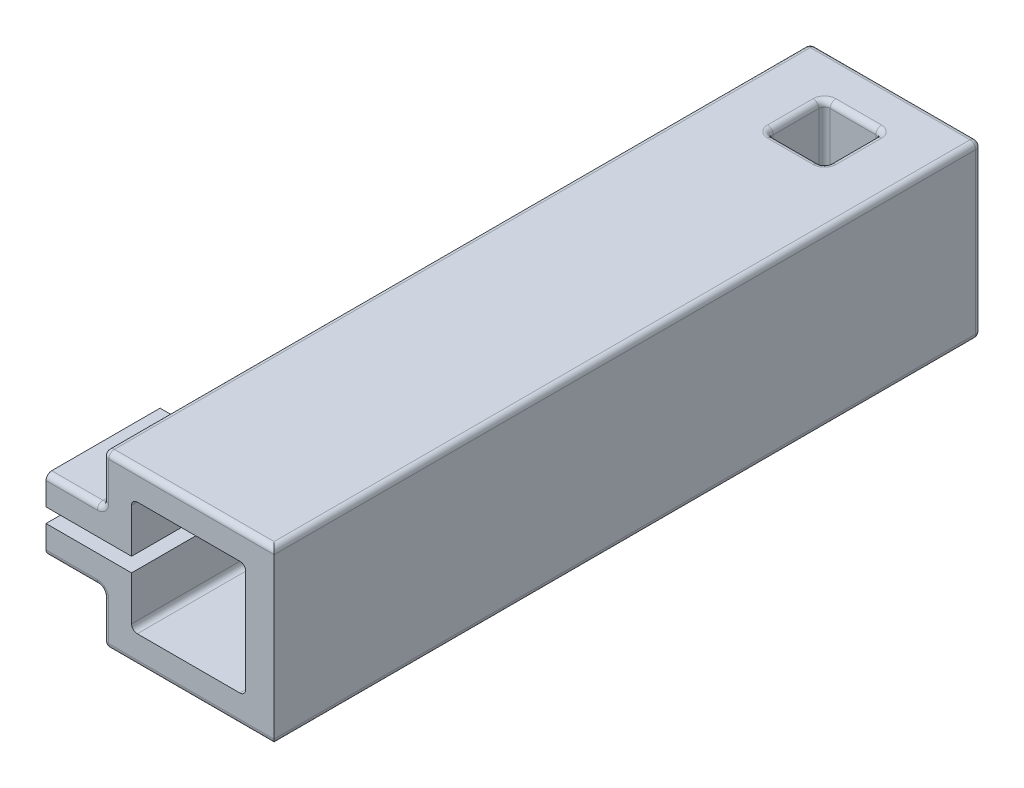
SolidWorks part; units mm, degrees
material "20% infill ABS"
ref_plane "Front Plane" through (0, 0, 0) normal (0, 0, 1) x (1, 0, 0)
ref_plane "Top Plane" through (0, 0, 0) normal (0, 1, 0) x (1, 0, 0)
ref_plane "Right Plane" through (0, 0, 0) normal (1, 0, 0) x (0, 0, -1)
sketch "Sketch1" plane through (0, 0, 0) normal (0, 0, 1) x (1, 0, 0)
  line L0 (-21.017, 13.2451) -> (-1.017, -6.7549)
  line L1 (-21.017, 13.2451) -> (-1.017, 13.2451)
  line L2 (-21.017, 13.2451) -> (-21.017, -6.7549)
  line L3 (-21.017, -6.7549) -> (-1.017, -6.7549)
  line L4 (-1.017, 13.2451) -> (-1.017, -6.7549)
  line L5 (-11.017, 3.2451) -> (-23.017, 3.2451)
  line L6 (-23.017, 15.2451) -> (0.983, 15.2451)
  line L7 (-23.017, 15.2451) -> (-23.017, -8.7549)
  line L8 (-23.017, -8.7549) -> (0.983, -8.7549)
  line L9 (0.983, 15.2451) -> (0.983, -8.7549)
  line L10 (-23.017, 15.2451) -> (0.983, -8.7549) construction
  line L11 (-23.017, -8.7549) -> (0.983, 15.2451) construction
  line L12 (-23.017, 3.2451) -> (-21.017, 3.2451)
  line L13 (-21.017, 4.5033) -> (-33.017, 4.5033)
  line L14 (-23.017, 4.5033) -> (-21.017, 4.5033)
  line L15 (-23.017, 4.5033) -> (-23.017, 1.9869)
  line L16 (-23.017, 1.9869) -> (-21.017, 1.9869)
  line L17 (-21.017, 4.5033) -> (-21.017, 1.9869)
  line L18 (-23.017, 4.5033) -> (-21.017, 1.9869) construction
  line L19 (-23.017, 1.9869) -> (-21.017, 4.5033) construction
  line L20 (-21.017, 1.9869) -> (-33.017, 1.9869)
  line L21 (-33.017, 4.5033) -> (-33.017, 6.5033)
  line L22 (-33.017, 1.9869) -> (-33.017, -0.0131)
  line L23 (-33.017, -0.0131) -> (-23.017, -0.0131)
  line L24 (-33.017, 6.5033) -> (-23.017, 6.5033)
  line L25 (-33.017, 1.9869) -> (-23.017, 1.9869)
  line L26 (-23.017, 1.9869) -> (-33.017, 1.9869)
  point P4 (-11.017, 3.2451)
  point P11 (-22.017, 3.2451)
  dimension "D1" = 20
  dimension "D2" = 20
  dimension "D3" = 24
  dimension "D4" = 24
extrude "Boss-Extrude1" add sketch "Sketch1" along normal blind 25 contours L16 L7 L8 L9 L6 L13 L2 L1 L4 L3 region at (-21.3564, 8.8742, 0)
sketch "Sketch2" plane through (-23.017, 0, 0) normal (-1, 0, 0) x (0, 0, 1)
  line L0 (25, 15.2451) -> (25, 4.5033) construction
  line L1 (0, 4.5033) -> (25, 4.5033)
  line L2 (0, 4.5033) -> (0, 6.5033)
  line L3 (0, 6.5033) -> (25, 6.5033)
  line L4 (25, 4.5033) -> (25, 6.5033)
  line L5 (25, 1.9869) -> (25, -8.7549) construction
  line L6 (0, 1.9869) -> (25, 1.9869)
  line L7 (0, 1.9869) -> (0, -0.0131)
  line L8 (0, -0.0131) -> (25, -0.0131)
  line L9 (25, 1.9869) -> (25, -0.0131)
  dimension "D1" = 2
  dimension "D2" = 2
extrude "Boss-Extrude2" add sketch "Sketch2" along normal blind 10 contours L2 L1 L4 L3 | L7 L6 L9 L8
sketch "Sketch3" plane through (0, 6.5033, 0) normal (0, 1, 0) x (1, 0, 0)
  line L0 (-23.017, 0) -> (-33.017, -25)
  circle A0 centre (-28.017, -12.5) radius 2.5
extrude "Cut-Extrude1" cut sketch "Sketch3" against normal blind 20 contours L0 A0 | L0 A0 region at (-27.0319, 6.5033, 12.8941) region at (-29.0022, 6.5033, 12.1059)
sketch "Sketch4" plane through (0, 6.5033, 0) normal (0, 1, 0) x (1, 0, 0)
  line L0 (-33.017, -25) -> (-32.017, -25)
  line L1 (-33.017, -25) -> (-23.017, -25) construction
  line L2 (-32.017, -25) -> (-32.017, -24)
  line L3 (-32.017, -24) -> (-33.017, -24)
  line L4 (-33.017, -24) -> (-33.017, -25)
  circle A0 centre (-32.017, -24) radius 1
  line M4 (-33.017, 0) -> (-33.017, -25)
  line M5 (-33.017, -25) -> (-23.017, -25)
extrude "Cut-Extrude2" cut sketch "Sketch4" against normal blind 20 contours A0 M4 M5 region at (-32.7937, 6.5033, 24.7766)
sketch "Sketch5" plane through (0, 6.5033, 0) normal (0, 1, 0) x (1, 0, 0)
  line L0 (-33.017, 0) -> (-32.017, 0)
  line L1 (-33.017, 0) -> (-23.017, 0) construction
  line L2 (-32.017, 0) -> (-32.017, -1)
  line L3 (-32.017, -1) -> (-33.017, -1)
  line L4 (-33.017, 0) -> (-33.017, -24) construction
  line L5 (-33.017, -1) -> (-33.017, 0)
  circle A0 centre (-32.017, -1) radius 1
  line M2 (-33.017, 0) -> (-33.017, -24)
  line M6 (-23.017, 0) -> (-33.017, 0)
extrude "Cut-Extrude3" cut sketch "Sketch5" against normal blind 20 contours A0 M6 M2 region at (-32.7937, 6.5033, 0.2234)
sketch "Sketch6" plane through (0, 0, 25) normal (0, 0, 1) x (1, 0, 0)
  line L0 (-21.017, 13.2451) -> (-21.017, 12.2451)
  line L1 (-21.017, 13.2451) -> (-21.017, 4.5033) construction
  line L2 (-21.017, 13.2451) -> (-20.017, 13.2451)
  line L3 (-21.017, 13.2451) -> (-1.017, 13.2451) construction
  line L4 (-21.017, 12.2451) -> (-20.017, 12.2451)
  line L5 (-20.017, 12.2451) -> (-20.017, 13.2451)
  circle A0 centre (-20.017, 12.2451) radius 1
  line M11 (-21.017, 4.5033) -> (-21.017, 13.2451)
  line M12 (-21.017, 13.2451) -> (-1.017, 13.2451)
extrude "Boss-Extrude4" add sketch "Sketch6" against normal blind 25 contours A0 M12 M11 region at (-20.7937, 13.0217, 25)
sketch "Sketch7" plane through (0, 0, 25) normal (0, 0, 1) x (1, 0, 0)
  line L0 (-1.017, 13.2451) -> (-1.017, 12.2451)
  line L1 (-1.017, 13.2451) -> (-1.017, -6.7549) construction
  line L2 (-1.017, 12.2451) -> (-2.017, 12.2451)
  line L3 (-2.017, 12.2451) -> (-2.017, 13.2451)
  line L4 (-20.017, 13.2451) -> (-1.017, 13.2451) construction
  line L5 (-1.017, 13.2451) -> (-2.017, 13.2451)
  circle A0 centre (-2.017, 12.2451) radius 1
  line M3 (-20.017, 13.2451) -> (-1.017, 13.2451)
  line M4 (-1.017, 13.2451) -> (-1.017, -6.7549)
extrude "Boss-Extrude5" add sketch "Sketch7" against normal blind 25 contours A0 M4 M3 region at (-1.2404, 13.0217, 25)
sketch "Sketch9" plane through (0, 0, 25) normal (0, 0, 1) x (1, 0, 0)
  line L0 (-1.017, -6.7549) -> (-2.017, -6.7549)
  line L1 (-21.017, -6.7549) -> (-1.017, -6.7549) construction
  line L2 (-1.017, -6.7549) -> (-1.017, -5.7549)
  line L3 (-1.017, 12.2451) -> (-1.017, -6.7549) construction
  line L4 (-1.017, -5.7549) -> (-2.017, -5.7549)
  line L5 (-2.017, -6.7549) -> (-2.017, -5.7549)
  circle A0 centre (-2.017, -5.7549) radius 1
  line M5 (-1.017, 12.2451) -> (-1.017, -6.7549)
  line M6 (-1.017, -6.7549) -> (-21.017, -6.7549)
extrude "Boss-Extrude6" add sketch "Sketch9" against normal blind 25 contours A0 M6 M5 region at (-1.2404, -6.5315, 25)
sketch "Sketch10" plane through (0, 0, 25) normal (0, 0, 1) x (1, 0, 0)
  line L0 (-21.017, -6.7549) -> (-20.017, -6.7549)
  line L1 (-21.017, -6.7549) -> (-2.017, -6.7549) construction
  line L2 (-21.017, -6.7549) -> (-21.017, -5.7549)
  line L3 (-21.017, 1.9869) -> (-21.017, -6.7549) construction
  line L4 (-20.017, -6.7549) -> (-20.017, -5.7549)
  line L5 (-20.017, -5.7549) -> (-21.017, -5.7549)
  circle A0 centre (-20.017, -5.7549) radius 1
  line M11 (-2.017, -6.7549) -> (-21.017, -6.7549)
  line M12 (-21.017, -6.7549) -> (-21.017, 1.9869)
extrude "Boss-Extrude7" add sketch "Sketch10" against normal blind 25 contours A0 M12 M11 region at (-20.7937, -6.5315, 25)
fillet "Fillet1" radius 1 4 edges at (-23.017, 15.2451, 12.5) (-23.017, -8.7549, 12.5) (0.983, -8.7549, 12.5) (0.983, 15.2451, 12.5)
fillet "Fillet2" radius 1 28 edges at (-23.017, 10.3742, 0) (-22.7241, 14.9522, 0) (-23.017, -3.884, 0) (-22.7241, -8.462, 0) (-11.017, -8.7549, 0) (0.6901, -8.462, 0) (0.983, 3.2451, 0) (0.6901, 14.9522, 0) (-27.517, 6.5033, 0) (-32.7241, 6.5033, 0.2929) (-32.7241, 6.5033, 24.7071) (-27.517, -0.0131, 0) (-32.7241, -0.0131, 0.2929) (-32.7241, -0.0131, 24.7071) (-11.017, 15.2451, 0) (-33.017, 6.5033, 12.5) (-33.017, -0.0131, 12.5) (-27.517, 6.5033, 25) (-27.517, -0.0131, 25) (-23.017, -3.884, 25) (-22.7241, -8.462, 25) (-11.017, -8.7549, 25) (0.6901, -8.462, 25) (0.983, 3.2451, 25) (0.6901, 14.9522, 25) (-11.017, 15.2451, 25) (-22.7241, 14.9522, 25) (-23.017, 10.3742, 25)
sketch "Sketch11" plane through (0, 15.2451, 0) normal (0, 1, 0) x (1, 0, 0)
  line L0 (-22.017, -1) -> (-0.017, -24)
  line L2 (-16.017, -17.5) -> (-6.017, -17.5)
  line L3 (-16.017, -17.5) -> (-16.017, -7.5)
  line L4 (-16.017, -7.5) -> (-6.017, -7.5)
  line L5 (-6.017, -17.5) -> (-6.017, -7.5)
  line L6 (-16.017, -17.5) -> (-6.017, -7.5) construction
  line L7 (-16.017, -7.5) -> (-6.017, -17.5) construction
  line L8 (-17.517, -6) -> (-4.517, -6)
  line L9 (-17.517, -6) -> (-17.517, -19)
  line L10 (-17.517, -19) -> (-4.517, -19)
  line L11 (-4.517, -6) -> (-4.517, -19)
  line L12 (-17.517, -6) -> (-4.517, -19) construction
  line L13 (-17.517, -19) -> (-4.517, -6) construction
  point P4 (-11.017, -12.5)
  point P9 (-11.017, -12.5)
  dimension "D1" = 10
  dimension "D2" = 10
  dimension "D3" = 13
  dimension "D4" = 13
extrude "Boss-Extrude8" add sketch "Sketch11" along normal blind 25 contours L11 L8 L0 L4 L5 L2 L10 | L9 L10 L0 L2 L3 L4 L8 region at (-10.8757, 15.2451, 6.1819) region at (-16.6484, 15.2451, 6.8757)
fillet "Fillet3" radius 1 4 edges at (-17.517, 27.7451, 6) (-4.517, 27.7451, 6) (-17.517, 27.7451, 19) (-4.517, 27.7451, 19)
ref_plane "Plane1" through (0, 0, 1) normal (0, 0, -1) x (-1, 0, 0)
sketch "Sketch12" plane through (0, 0, 1) normal (0, 0, -1) x (-1, 0, 0)
  line L0 (0.017, 15.2451) -> (22.017, 15.2451)
  line L1 (23.017, 14.2451) -> (23.017, 6.5033)
  line L2 (23.017, 6.5033) -> (32.017, 6.5033)
  line L3 (33.017, 5.5033) -> (33.017, 4.5033)
  line L4 (33.017, 4.5033) -> (21.017, 4.5033)
  line L5 (21.017, 4.5033) -> (21.017, 12.2451)
  line L6 (20.017, 13.2451) -> (2.017, 13.2451)
  line L7 (1.017, 12.2451) -> (1.017, -5.7549)
  line L8 (2.017, -6.7549) -> (20.017, -6.7549)
  line L9 (21.017, -5.7549) -> (21.017, 1.9869)
  line L10 (21.017, 1.9869) -> (32.017, 1.9869)
  line L11 (32.017, 1.9869) -> (33.017, 1.9869)
  line L12 (33.017, 1.9869) -> (33.017, 0.9869)
  line L13 (32.017, -0.0131) -> (23.017, -0.0131)
  line L14 (23.017, -0.0131) -> (23.017, -7.7549) construction
  line L15 (23.017, -0.0131) -> (23.017, -7.7549)
  line L16 (22.017, -8.7549) -> (0.017, -8.7549)
  line L17 (-0.983, -7.7549) -> (-0.983, 14.2451)
  line L18 (-0.983, -7.7549) -> (-0.983, 14.2451) construction
  arc A0 (0.017, 15.2451) -> (-0.983, 14.2451) centre (0.017, 14.2451) ccw construction
  arc A1 (-0.983, 14.2451) -> (0.017, 15.2451) centre (0.017, 14.2451) cw
  arc A2 (1.017, 12.2451) -> (2.017, 13.2451) centre (2.017, 12.2451) cw
  arc A3 (20.017, 13.2451) -> (21.017, 12.2451) centre (20.017, 12.2451) cw
  arc A4 (23.017, 14.2451) -> (22.017, 15.2451) centre (22.017, 14.2451) ccw
  arc A5 (32.017, 6.5033) -> (33.017, 5.5033) centre (32.017, 5.5033) cw
  arc A6 (32.017, -0.0131) -> (33.017, 0.9869) centre (32.017, 0.9869) ccw
  arc A7 (20.017, -6.7549) -> (21.017, -5.7549) centre (20.017, -5.7549) ccw
  arc A8 (22.017, -8.7549) -> (23.017, -7.7549) centre (22.017, -7.7549) ccw
  arc A9 (1.017, -5.7549) -> (2.017, -6.7549) centre (2.017, -5.7549) ccw
  arc A10 (-0.983, -7.7549) -> (0.017, -8.7549) centre (0.017, -7.7549) ccw
extrude "Boss-Extrude9" add sketch "Sketch12" along normal blind 100
sketch "Sketch14" plane through (0, 6.5033, 0) normal (0, 1, 0) x (1, 0, 0)
  line L0 (-23.017, 99) -> (-23.017, -1)
  line L1 (-23.017, 99) -> (-23.017, -24) construction
  line L2 (-23.017, -1) -> (-23.017, 29)
  line L3 (-23.017, 29) -> (-32.017, 29)
  line L4 (-32.017, 99) -> (-32.017, -24) construction
  line L5 (-23.017, 99) -> (-23.017, 68.8479)
  line L6 (-23.017, 68.8479) -> (-32.017, 68.8479)
  circle A0 centre (-27.517, 29) radius 2.5
  circle A1 centre (-27.517, 68.8479) radius 2.5
extrude "Cut-Extrude4" cut sketch "Sketch14" against normal blind 20 contours L6 A1 | L6 A1 | L3 A0 | L3 A0 region at (-27.517, 6.5033, -27.939) region at (-27.517, 6.5033, -30.061) region at (-27.517, 6.5033, -67.7869) region at (-27.517, 6.5033, -69.9089)
sketch "Sketch15" plane through (0, 15.2451, 0) normal (0, 1, 0) x (1, 0, 0)
  line L0 (-16.017, -7.5) -> (-6.017, -17.5)
  line L1 (-16.017, -17.5) -> (-6.017, -17.5) construction
  line L2 (-6.017, -7.5) -> (-16.017, -7.5)
  line L3 (-6.017, -7.5) -> (-6.017, -17.5)
  line L4 (-6.017, -17.5) -> (-16.017, -17.5)
  line L5 (-16.017, -7.5) -> (-16.017, -17.5)
  line L6 (-6.017, -7.5) -> (-16.017, -17.5) construction
  line L7 (-6.017, -17.5) -> (-16.017, -7.5) construction
  line L8 (-16.017, -17.5) -> (-6.017, -17.5) construction
  point P4 (-11.017, -12.5)
  line M1 (-6.017, -7.5) -> (-16.017, -7.5)
  line M2 (-16.017, -7.5) -> (-16.017, -17.5)
  line M3 (-16.017, -17.5) -> (-6.017, -17.5)
  line M4 (-6.017, -17.5) -> (-6.017, -7.5)
extrude "Cut-Extrude5" cut sketch "Sketch15" against normal blind 23 contours L0 M1 M4 | L0 M2 M3 region at (-9.3504, 15.2451, 10.8333) region at (-12.6837, 15.2451, 14.1667)
sketch "Sketch16" plane through (-4.517, 0, 0) normal (1, 0, 0) x (0, 0, -1)
  line L0 (-18, 15.2451) -> (-7, 40.2451)
  line L1 (-24, 15.2451) -> (99, 15.2451) construction
  line L2 (-21.678, 40.2451) -> (-3.322, 40.2451)
  line L3 (-21.678, 40.2451) -> (-21.678, 15.2451)
  line L4 (-21.678, 15.2451) -> (-3.322, 15.2451)
  line L5 (-3.322, 40.2451) -> (-3.322, 15.2451)
  line L6 (-21.678, 40.2451) -> (-3.322, 15.2451) construction
  line L7 (-21.678, 15.2451) -> (-3.322, 40.2451) construction
  point P4 (-12.5, 27.7451)
  line M1 (-18, 15.2451) -> (-7, 15.2451)
  line M2 (-7, 15.2451) -> (-7, 40.2451)
  line M3 (-7, 40.2451) -> (-18, 40.2451)
  line M4 (-18, 40.2451) -> (-18, 15.2451)
extrude "Cut-Extrude6" cut sketch "Sketch16" against normal blind 43 contours L0 M4 M3 | L0 M1 M2 | L5 L2 L4 M2 | L3 L4 L2 M4 region at (-4.517, 31.9118, 14.3333) region at (-4.517, 23.5784, 10.6667) region at (-4.517, 27.7451, 19.839) region at (-4.517, 27.7451, 5.161)
fillet "Fillet4" radius 1 24 edges at (-33.017, 1.4869, -99) (-32.7241, 0.2798, -99) (-33.017, 5.0033, -99) (-32.7241, 6.2104, -99) (-21.017, -1.884, -99) (-20.7241, -6.462, -99) (-11.017, -6.7549, -99) (-1.3099, -6.462, -99) (-1.017, 3.2451, -99) (-1.3099, 12.9522, -99) (-21.017, 8.3742, -99) (-20.7241, 12.9522, -99) (-23.017, 10.3742, -99) (-22.7241, 14.9522, -99) (-23.017, -3.884, -99) (-22.7241, -8.462, -99) (-11.017, -8.7549, -99) (0.6901, -8.462, -99) (0.983, 3.2451, -99) (0.6901, 14.9522, -99) (-27.517, -0.0131, -99) (-27.517, 6.5033, -99) (-11.017, 13.2451, -99) (-11.017, 15.2451, -99)
sketch "Sketch17" plane through (0, -7.7549, 0) normal (0, 1, 0) x (1, 0, 0)
  line L0 (-16.017, -7.5) -> (-6.017, -7.5)
  line L1 (-6.017, -7.5) -> (-6.017, -17.5)
  line L2 (-6.017, -17.5) -> (-16.017, -17.5)
  line L3 (-16.017, -17.5) -> (-16.017, -7.5)
extrude "Cut-Extrude7" cut sketch "Sketch17" against normal blind 43
ref_plane "Plane2" through (0, 0, 25) normal (0, 0, 1) x (1, 0, 0)
sketch "Sketch18" plane through (0, 0, 25) normal (0, 0, 1) x (1, 0, 0)
  line L0 (-32.017, 4.5033) -> (-23.017, 4.5033)
  line L1 (-21.017, 4.5033) -> (-32.017, 4.5033) construction
  line L2 (-23.017, 4.5033) -> (-23.017, 6.5033)
  line L3 (-23.017, 6.5033) -> (-33.017, 6.5033)
  line L4 (-23.017, -0.0131) -> (-33.017, -0.0131)
  line L5 (-33.017, -0.0131) -> (-33.017, 6.5033)
  line L6 (-23.017, 6.5033) -> (-23.017, -0.0131)
extrude "Cut-Extrude8" cut sketch "Sketch18" against normal blind 104 contours L6 L2 L3 L5 L4 region at (-28.017, 3.2451, 25)
fillet "Fillet5" radius 1 2 edges at (-23.017, 1.4869, 25) (-23.017, 5.0033, 25)
fillet "Fillet6" radius 1 6 edges at (-33.017, 1.4869, -79) (-32.7241, 0.2798, -79) (-33.017, 5.0033, -79) (-32.7241, 6.2104, -79) (-27.517, -0.0131, -79) (-27.517, 6.5033, -79)
sketch "Sketch19" plane through (0, 6.5033, 0) normal (0, 1, 0) x (1, 0, 0)
  line L0 (-32.017, 98) -> (-23.017, 80)
  line L1 (-32.017, 80) -> (-23.017, 80) construction
  line L2 (-23.017, 80) -> (-23.017, 79) construction
  line L3 (-32.017, 80) -> (-23.017, 98)
  circle A0 centre (-27.517, 89) radius 2.5
extrude "Cut-Extrude9" cut sketch "Sketch19" against normal blind 14 contours L0 A0 L3 | L3 A0 L0 | L0 A0 L3 | L3 A0 L0 region at (-27.517, 6.5033, -90.6076) region at (-28.8635, 6.5033, -89) region at (-26.1706, 6.5033, -89) region at (-27.517, 6.5033, -87.3924)
sketch "Sketch20" plane through (0, 0, -99) normal (0, 0, -1) x (-1, 0, 0)
  line L0 (0.017, -7.7549) -> (22.017, 14.2451)
  line L1 (22.017, -7.7549) -> (0.017, 14.2451)
  line L2 (22.017, 4.5033) -> (32.017, 4.5033) construction
  line L3 (0.9804, -6.7915) -> (21.0537, -6.7915)
  line L4 (0.9804, -6.7915) -> (0.9804, 13.2818)
  line L5 (0.9804, 13.2818) -> (21.0537, 13.2818)
  line L6 (21.0537, -6.7915) -> (21.0537, 13.2818)
  line L7 (0.9804, -6.7915) -> (21.0537, 13.2818) construction
  line L8 (0.9804, 13.2818) -> (21.0537, -6.7915) construction
  line L9 (-3.983, -11.7549) -> (26.017, -11.7549)
  line L10 (-3.983, -11.7549) -> (-3.983, 18.2451)
  line L11 (-3.983, 18.2451) -> (26.017, 18.2451)
  line L12 (26.017, -11.7549) -> (26.017, 18.2451)
  line L13 (-3.983, -11.7549) -> (26.017, 18.2451) construction
  line L14 (-3.983, 18.2451) -> (26.017, -11.7549) construction
  line L15 (21.017, 1.9869) -> (26.017, 1.9869)
  line L16 (21.017, 1.9869) -> (21.017, 4.5033)
  line L17 (21.017, 4.5033) -> (26.017, 4.5033)
  line L18 (26.017, 1.9869) -> (26.017, 4.5033)
  point P8 (11.017, 3.2451)
  point P13 (11.017, 3.2451)
  line M2 (0.017, -7.7549) -> (2.017, -7.7549)
  arc M3 (2.017, -7.7549) -> (0.017, -5.7549) centre (2.017, -5.7549) cw
  line M4 (0.017, -5.7549) -> (0.017, -7.7549)
  dimension "D1" = 30
extrude "Boss-Extrude10" add sketch "Sketch20" against normal blind 124 contours L6 L17 L12 L11 L10 L9 L15 L3 L4 L5 M3 M2 M4 region at (-11.017, -7.2158, -99)
sketch "Sketch21" plane through (0, -11.7549, 0) normal (0, -1, 0) x (-1, 0, 0)
  line L0 (-3.983, 99) -> (11.017, 99)
  line L1 (-3.983, 99) -> (26.017, 99) construction
  line L2 (11.017, 99) -> (11.017, 91.5)
  line L3 (11.017, 91.5) -> (16.017, 91.5)
  line L4 (16.017, 91.5) -> (16.017, 81.5)
  line L5 (16.017, 81.5) -> (6.017, 81.5)
  line L6 (6.017, 81.5) -> (6.017, 91.5)
  line L7 (6.017, 91.5) -> (11.017, 91.5)
extrude "Cut-Extrude10" cut sketch "Sketch21" against normal blind 124 contours L7 L6 L5 L4 L3 region at (-11.017, -11.7549, -86.5)
sketch "Sketch22" plane through (0, 0, -99) normal (0, 0, -1) x (-1, 0, 0)
  line L0 (26.017, 1.9869) -> (26.017, 4.5033)
  line L2 (26.017, 1.9869) -> (36.017, 1.9869)
  line L3 (26.017, 1.9869) -> (26.017, -3.0131)
  line L4 (26.017, -3.0131) -> (36.017, -3.0131)
  line L5 (36.017, 1.9869) -> (36.017, -3.0131)
  line L6 (26.017, 4.5033) -> (36.017, 4.5033)
  line L7 (26.017, 4.5033) -> (26.017, 9.5033)
  line L8 (26.017, 9.5033) -> (36.017, 9.5033)
  line L9 (36.017, 4.5033) -> (36.017, 9.5033)
  line M6 (21.0537, 4.5033) -> (32.017, 4.5033)
  line M7 (32.017, 4.5033) -> (32.017, 5.5033)
  line M8 (32.017, 5.5033) -> (26.017, 5.5033)
  line M9 (26.017, 5.5033) -> (26.017, 18.2451)
  line M13 (26.017, -11.7549) -> (26.017, 0.9869)
  line M14 (26.017, 0.9869) -> (32.017, 0.9869)
  line M15 (32.017, 0.9869) -> (32.017, 1.9869)
  line M16 (32.017, 1.9869) -> (21.0537, 1.9869)
  dimension "D1" = 5
  dimension "D2" = 5
  dimension "D3" = 10
  dimension "D4" = 10
extrude "Boss-Extrude11" add sketch "Sketch22" against normal blind 20 contours L3 M16 M14 M15 | L5 L2 L4 M15 M14 M13 | L7 M6 M7 M8 | L6 L9 L8 M9 M8 M7 region at (-29.017, 5.0033, -99) region at (-29.017, 1.4869, -99) region at (-31.2898, -0.7858, -99) region at (-31.2898, 7.276, -99)
fillet "Fillet7" radius 1 8 edges at (-11.017, -11.7549, 25) (3.983, -11.7549, -37) (-26.017, -11.7549, -37) (-11.017, -11.7549, -99) (3.983, 18.2451, -37) (-26.017, 18.2451, -37) (-11.017, 18.2451, 25) (-11.017, 18.2451, -99)
sketch "Sketch25" plane through (0, 0, -99) normal (0, 0, -1) x (-1, 0, 0)
  line L0 (-3.983, -10.7549) -> (26.017, 17.2451)
  line L1 (-3.983, 17.2451) -> (26.017, -10.7549)
  line L3 (0.9804, 13.2818) -> (21.0537, 13.2818)
  line L4 (0.9804, 13.2818) -> (0.9804, -6.7915)
  line L5 (0.9804, -6.7915) -> (21.0537, -6.7915)
  line L6 (21.0537, 13.2818) -> (21.0537, -6.7915)
  line L7 (0.9804, 13.2818) -> (21.0537, -6.7915) construction
  line L8 (0.9804, -6.7915) -> (21.0537, 13.2818) construction
  point P8 (11.017, 3.2451)
  line M7 (21.0537, 1.9869) -> (21.0537, -6.7915)
  line M8 (21.0537, -6.7915) -> (0.9804, -6.7915)
  line M9 (0.9804, -6.7915) -> (0.9804, 13.2818)
  line M10 (0.9804, 13.2818) -> (21.0537, 13.2818)
  line M11 (21.0537, 13.2818) -> (21.0537, 4.5033)
extrude "Boss-Extrude12" add sketch "Sketch25" against normal blind 23 contours L1 L0 M9 | L1 L0 M9 M11 M10 | L6 L0 L1 M11 M7 | L1 L0 M9 M8 M7 region at (-4.3259, 3.2451, -99) region at (-11.017, -3.4321, -99) region at (-11.017, 9.9223, -99) region at (-17.7081, 3.2451, -99)
sketch "Sketch26" plane through (0, 13.2818, 0) normal (0, 1, 0) x (1, 0, 0)
  line L0 (-6.017, 81.5) -> (-16.017, 91.5)
  line L1 (-6.017, 91.5) -> (-16.017, 81.5)
  line L3 (-6.017, 81.5) -> (-16.017, 81.5)
  line L4 (-6.017, 81.5) -> (-6.017, 91.5)
  line L5 (-6.017, 91.5) -> (-16.017, 91.5)
  line L6 (-16.017, 81.5) -> (-16.017, 91.5)
  line L7 (-6.017, 81.5) -> (-16.017, 91.5) construction
  line L8 (-6.017, 91.5) -> (-16.017, 81.5) construction
  point P8 (-11.017, 86.5)
  line M1 (-6.017, 91.5) -> (-16.017, 91.5)
  line M2 (-16.017, 91.5) -> (-16.017, 81.5)
  line M3 (-16.017, 81.5) -> (-6.017, 81.5)
  line M4 (-6.017, 81.5) -> (-6.017, 91.5)
extrude "Cut-Extrude14" cut sketch "Sketch26" against normal blind 43 contours L1 L0 M4 | L0 L1 M3 | L1 L0 M2 | L1 L0 M1 region at (-11.017, 13.2818, -83.1667) region at (-7.6837, 13.2818, -86.5) region at (-14.3504, 13.2818, -86.5) region at (-11.017, 13.2818, -89.8333)
sketch "Sketch27" plane through (0, 0, -99) normal (0, 0, -1) x (-1, 0, 0)
  line L0 (26.017, 9.5033) -> (26.017, -3.0131)
  line L1 (26.017, 1.9869) -> (21.0537, 1.9869)
  line L2 (21.0537, 1.9869) -> (21.0537, 4.5033)
  line L3 (21.0537, 4.5033) -> (26.017, 4.5033)
  line L4 (26.017, 4.5033) -> (26.017, 1.9869)
  line M1 (36.017, 1.9869) -> (21.0537, 1.9869)
  line M2 (21.0537, 1.9869) -> (21.0537, 4.5033)
  line M3 (21.0537, 4.5033) -> (36.017, 4.5033)
extrude "Boss-Extrude13" add sketch "Sketch27" against normal blind 23 contours L0 M3 M2 M1 region at (-23.5354, 3.2451, -99)
sketch "Sketch28" plane through (0, 0, -79) normal (0, 0, 1) x (1, 0, 0)
  line L1 (-36.017, 9.5033) -> (-26.017, 9.5033)
  line L2 (-36.017, 9.5033) -> (-36.017, 4.5033)
  line L3 (-36.017, 4.5033) -> (-26.017, 4.5033)
  line L4 (-26.017, 9.5033) -> (-26.017, 4.5033)
  line L5 (-36.017, 1.9869) -> (-26.017, 1.9869)
  line L6 (-36.017, 1.9869) -> (-36.017, -3.0131)
  line L7 (-36.017, -3.0131) -> (-26.017, -3.0131)
  line L8 (-26.017, 1.9869) -> (-26.017, -3.0131)
extrude "Cut-Extrude15" cut sketch "Sketch28" against normal blind 23
sketch "Sketch29" plane through (0, 0, 25) normal (0, 0, 1) x (1, 0, 0)
  line L1 (-21.017, 4.5033) -> (-36.017, 4.5033)
  line L2 (-21.017, 4.5033) -> (-21.017, 9.5033)
  line L3 (-21.017, 9.5033) -> (-36.017, 9.5033)
  line L4 (-36.017, 4.5033) -> (-36.017, 9.5033)
  line L5 (-21.017, 1.9869) -> (-36.017, 1.9869)
  line L6 (-21.017, 1.9869) -> (-21.017, -3.0131)
  line L7 (-21.017, -3.0131) -> (-36.017, -3.0131)
  line L8 (-36.017, 1.9869) -> (-36.017, -3.0131)
  dimension "D1" = 5
  dimension "D2" = 5
  dimension "D3" = 15
  dimension "D4" = 15
extrude "Boss-Extrude14" add sketch "Sketch29" against normal blind 20
sketch "Sketch31" plane through (0, 13.2818, 0) normal (0, -1, 0) x (-1, 0, 0)
  line L1 (16.017, -17.5) -> (5.6158, -17.5)
  line L2 (16.017, -17.5) -> (16.017, -6.4498)
  line L3 (16.017, -6.4498) -> (5.6158, -6.4498)
  line L4 (5.6158, -17.5) -> (5.6158, -6.4498)
extrude "Boss-Extrude15" add sketch "Sketch31" along normal blind 0.04
sketch "Sketch32" plane through (0, -6.7549, 0) normal (0, 1, 0) x (1, 0, 0)
  line L1 (-6.017, -7.5) -> (-16.017, -7.5)
  line L2 (-6.017, -7.5) -> (-6.017, -17.5)
  line L3 (-6.017, -17.5) -> (-16.017, -17.5)
  line L4 (-16.017, -7.5) -> (-16.017, -17.5)
extrude "Boss-Extrude16" add sketch "Sketch32" along normal blind 50.04 and the other way blind 10.04
sketch "Sketch33" plane through (0, 0, 17.5) normal (0, 0, 1) x (1, 0, 0)
  line L0 (-20.017, -6.7549) -> (-2.017, -6.7549) construction
  line L1 (-16.017, 13.2451) -> (-6.017, 13.2451)
  line L2 (-16.017, 13.2451) -> (-16.017, -6.7549)
  line L3 (-16.017, -6.7549) -> (-6.017, -6.7549)
  line L4 (-6.017, 13.2451) -> (-6.017, -6.7549)
  line L5 (-2.017, -6.7549) -> (-20.017, -6.7549) construction
extrude "Cut-Extrude16" cut sketch "Sketch33" against normal blind 10
sketch "Sketch34" plane through (0, 13.2451, 0) normal (0, -1, 0) x (-1, 0, 0)
  line L1 (16.017, -6.4498) -> (5.6158, -6.4498)
  line L2 (16.017, -6.4498) -> (16.017, -17.5)
  line L3 (16.017, -17.5) -> (5.6158, -17.5)
  line L4 (5.6158, -6.4498) -> (5.6158, -17.5)
extrude "Boss-Extrude17" add sketch "Sketch34" along normal blind 10 and the other way blind 10.0001
sketch "Sketch35" plane through (0, 0, 17.5) normal (0, 0, 1) x (1, 0, 0)
  line L1 (-16.017, 3.2451) -> (-5.6158, 3.2451)
  line L2 (-16.017, 3.2451) -> (-16.017, 13.2451)
  line L3 (-16.017, 13.2451) -> (-5.6158, 13.2451)
  line L4 (-5.6158, 3.2451) -> (-5.6158, 13.2451)
extrude "Cut-Extrude17" cut sketch "Sketch35" against normal blind 20
sketch "Sketch36" plane through (0, 0, 17.5) normal (0, 0, 1) x (1, 0, 0)
  line L0 (-6.017, -16.7949) -> (-6.017, -11.7549) construction
  line L1 (-16.017, -16.7949) -> (-6.017, -16.7949)
  line L2 (-16.017, -16.7949) -> (-16.017, -11.7549)
  line L3 (-16.017, -11.7549) -> (-6.017, -11.7549)
  line L4 (-6.017, -16.7949) -> (-6.017, -11.7549)
  dimension "D1" = 5.04
extrude "Cut-Extrude18" cut sketch "Sketch36" against normal blind 20
sketch "Sketch37" plane through (0, 0, 17.5) normal (0, 0, 1) x (1, 0, 0)
  line L1 (-16.017, 18.2451) -> (-4.7364, 18.2451)
  line L2 (-16.017, 18.2451) -> (-16.017, 43.736)
  line L3 (-16.017, 43.736) -> (-4.7364, 43.736)
  line L4 (-4.7364, 18.2451) -> (-4.7364, 43.736)
extrude "Cut-Extrude19" cut sketch "Sketch37" against normal blind 30
ref_plane "Plane3" through (2.983, 18.2451, 24) normal (0, 0, -1) x (-1, 0, 0)
fillet "Fillet8" radius 1 21 edges at (-31.017, -3.0131, 25) (-31.017, 4.5033, 5) (-31.017, 1.9869, 5) (-25.7241, -11.462, 24.7071) (-25.7241, -11.462, -98.7071) (-25.7241, 17.9522, -98.7071) (-25.7241, 17.9522, 24.7071) (3.6901, -11.462, -98.7071) (3.6901, 17.9522, -98.7071) (-26.017, -6.884, 25) (-26.017, 3.2451, -99) (-26.017, 13.3742, 25) (-26.017, 9.5033, 15) (-26.017, 7.0033, 5) (-26.017, 4.5033, -35.5) (-26.017, 3.2451, -76) (-26.017, 1.9869, -35.5) (-26.017, -0.5131, 5) (-26.017, -3.0131, 15) (-31.017, 9.5033, 25) (3.983, 3.2451, -99)
fillet "Fillet9" radius 1 12 edges at (-11.017, 18.2451, -81.5) (-11.017, -11.7549, -81.5) (-11.017, 18.2451, -91.5) (-11.017, -11.7549, -91.5) (-6.017, 18.2451, -86.5) (-6.017, 3.2451, -81.5) (-6.017, -11.7549, -86.5) (-6.017, 3.2451, -91.5) (-16.017, 18.2451, -86.5) (-16.017, 3.2451, -91.5) (-16.017, -11.7549, -86.5) (-16.017, 3.2451, -81.5)
sketch "Sketch38" plane through (0, 9.5033, 0) normal (0, 1, 0) x (1, 0, 0)
  line L0 (-36.017, -5) -> (-36.017, -14.5)
  line L1 (-36.017, -5) -> (-36.017, -24) construction
  line L2 (-36.017, -14.5) -> (-31.017, -14.5)
  circle A0 centre (-31.017, -14.5) radius 2
extrude "Cut-Extrude20" cut sketch "Sketch38" against normal blind 20 contours A0 region at (-31.017, 9.5033, 16.4434)
